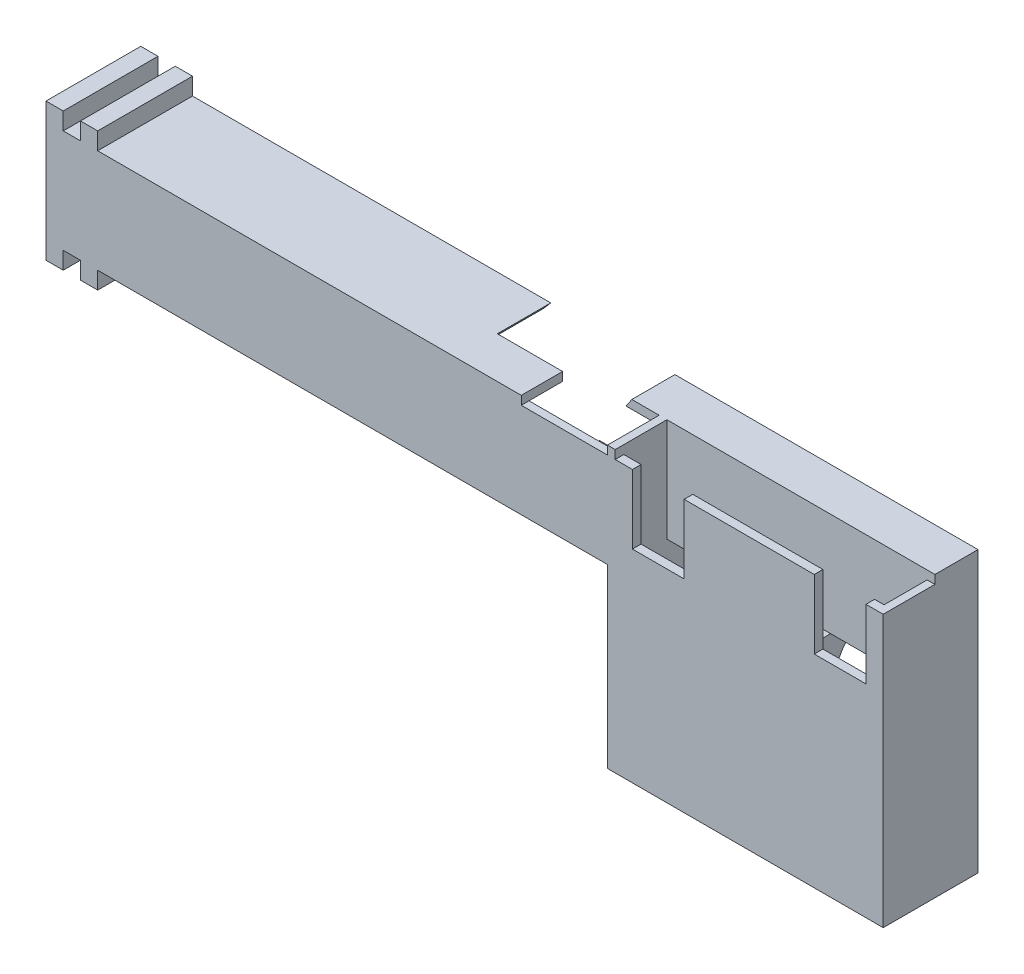
SolidWorks part; units mm, degrees
ref_plane "Front Plane" through (0, 0, 0) normal (0, 0, 1) x (1, 0, 0)
ref_plane "Top Plane" through (0, 0, 0) normal (0, 1, 0) x (1, 0, 0)
ref_plane "Right Plane" through (0, 0, 0) normal (1, 0, 0) x (0, 0, -1)
sketch "Sketch1" plane through (0, 0, 0) normal (0, 0, 1) x (1, 0, 0)
  line L3 (0, 20.5) -> (32, 20.5)
  line L4 (0.9, 20.5) -> (0.9, 31.5)
  line L5 (31.1, 20.5) -> (31.1, 31.5)
  line L6 (0.9, 31.5) -> (31.1, 31.5)
  line L7 (0.9, 20.5) -> (0.9, 6)
  line L8 (31.1, 20.5) -> (31.1, 6)
  line L9 (0.9, 6) -> (31.1, 6)
  line L10 (0, 20.5) -> (0, 0)
  line L11 (0, 0) -> (32, 0)
  line L12 (32, 0) -> (32, 20.5)
  line L13 (0, 20.5) -> (0, 31.5)
  line L14 (0, 31.5) -> (0.9, 31.5)
  line L15 (0, 31.5) -> (0.9, 31.5)
  line L16 (32, 20.5) -> (32, 31.5)
  line L17 (32, 31.5) -> (31.1, 31.5)
  line L21 (0, 31.5) -> (0.9, 31.5)
  line L22 (31.1, 31.5) -> (32, 31.5)
  line L31 (0, 31.5) -> (32, 31.5)
  line L41 (12.1, 20.5) -> (19.9, 20.5)
  line L42 (12.1, 20.5) -> (12.1, 6)
  line L43 (12.1, 6) -> (19.9, 6)
  line L44 (19.9, 20.5) -> (19.9, 6)
  point P0 (0, 0)
  point P11 (0, 20.5)
  point P32 (16, 6)
  point P40 (16, 20.5)
  dimension "D2" = 6
  dimension "D3" = 0.9
  dimension "D6" = 11
  dimension "D7" = 14.5
  dimension "D8" = 0.9
  dimension "D9" = 32
  dimension "D18" = 7.8
  dimension "D19" = 3.9
extrude "Boss-Extrude2" add sketch "Sketch1<3>" along normal blind 11 contours L11 L12 L3 L8 L9 L7 L10 | L14 L13 L3 L4 | L16 L17 L5 L3 | L4 L14 L13 region at (0.45, 26, 0) region at (16, 4.2266, 0) region at (31.55, 26, 0)
sketch "Sketch1<3>" plane through (0, 0, 0) normal (0, 0, 1) x (1, 0, 0) same geometry as "Sketch1"
extrude "Boss-Extrude3" add sketch "Sketch1<4>" along normal blind 5 contours L6 L4 L3 L5 region at (16, 26, 0)
sketch "Sketch1<4>" plane through (0, 0, 0) normal (0, 0, 1) x (1, 0, 0) same geometry as "Sketch1"
sketch "Sketch2" plane through (0, 6, 0) normal (0, 1, 0) x (1, 0, 0)
  line L0 (0.9, -11) -> (0.9, -10)
  line L1 (0.9, -11) -> (0.9, -5) construction
  line L2 (31.1, -11) -> (31.1, -10)
  line L3 (31.1, -11) -> (31.1, 0) construction
  line L4 (0.9, -10) -> (31.1, -10)
  line L5 (0.9, -11) -> (31.1, -11)
  dimension "D1" = 1
extrude "Boss-Extrude4" add sketch "Sketch2" along normal blind 25.5
extrude "Boss-Extrude5" add sketch "Sketch1" along normal blind 11 contours L44 L3 L42 L9 region at (16, 13.25, 0)
sketch "Sketch3" plane through (0, 0, 10) normal (0, 0, -1) x (-1, 0, 0)
  line L0 (-12.1, 6) -> (-12.1, 20.5) construction
  line L1 (-0.9, 6) -> (-12.1, 6)
  line L2 (-0.9, 6) -> (-0.9, 17)
  line L3 (-0.9, 17) -> (-12.1, 17)
  line L4 (-12.1, 6) -> (-12.1, 17)
  line L5 (-19.9, 6) -> (-19.9, 20.5) construction
  line L6 (-31.1, 6) -> (-19.9, 6)
  line L7 (-31.1, 6) -> (-31.1, 17)
  line L8 (-31.1, 17) -> (-19.9, 17)
  line L9 (-19.9, 6) -> (-19.9, 17)
  dimension "D1" = 11
  dimension "D2" = 11
extrude "Boss-Extrude6" add sketch "Sketch3" along normal blind 5
sketch "Sketch4" plane through (0, 31.5, 0) normal (0, 1, 0) x (1, 0, 0)
  line L0 (0, 0) -> (32, 0) construction
  line L1 (0, -0.4) -> (31.1, -0.4)
  line L2 (0, -0.4) -> (0, -4.4)
  line L3 (0, -4.4) -> (31.1, -4.4)
  line L4 (31.1, -0.4) -> (31.1, -4.4)
  line L6 (31.1, -10) -> (31.1, -5) construction
  line L8 (0, -11) -> (0, 0) construction
  dimension "D1" = 0.4
  dimension "D2" = 4
extrude "Cut-Extrude1" cut sketch "Sketch4" against normal blind 10
sketch "Sketch5" plane through (0, 31.5, 0) normal (0, 1, 0) x (1, 0, 0)
  line L0 (0, -11) -> (0, -4.4) construction
  line L1 (32, 0) -> (0, 0)
  line L2 (32, 0) -> (32, -5)
  line L3 (32, -5) -> (0, -5)
  line L4 (0, 0) -> (0, -5)
  line L5 (0.9, -5) -> (31.1, -5) construction
extrude "Boss-Extrude7" add sketch "Sketch5" along normal blind 1
sketch "Sketch7" plane through (0, 0, 0) normal (-1, 0, 0) x (0, 0, 1)
  line L0 (0, 32.5) -> (0, 0) construction
  line L1 (5, 32.5) -> (0, 32.5)
  line L2 (5, 32.5) -> (5, 31.5)
  line L3 (5, 31.5) -> (0, 31.5)
  line L4 (0, 32.5) -> (0, 31.5)
  line L5 (11, 31.5) -> (5, 31.5) construction
  line L6 (4.4, 21.5) -> (4.4, 31.5) construction
  line L7 (0, 21.5) -> (5, 21.5)
  line L8 (0, 21.5) -> (0, 20.4962)
  line L9 (0, 20.4962) -> (5, 20.4962)
  line L10 (5, 21.5) -> (5, 20.4962)
  line L11 (5, 31.5) -> (5, 21.5)
  line L12 (4.4, 31.5) -> (4.4, 21.5)
  line M5 (0.4, 31.5) -> (4.4, 31.5)
  line M7 (4.4, 21.5) -> (0.4, 21.5)
  line M10 (5, 31.5) -> (5, 32.5)
  line M11 (5, 32.5) -> (0, 32.5)
  line M12 (0, 32.5) -> (0, 0)
  dimension "D1" = 1.0038
  dimension "D2" = 5
extrude "Boss-Extrude8" add sketch "Sketch7" along normal blind 62.24 contours L10 L7 L9 M7 M12 | L3 M10 M11 M12 M5 region at (0, 32, 2.5) region at (0, 20.9981, 2.5)
sketch "Sketch8" plane through (0, 0, 5) normal (0, 0, 1) x (1, 0, 0)
  line L0 (-62.24, 32.5) -> (32, 32.5) construction
  line L1 (0.9, 31.5) -> (0, 31.5)
  line L2 (0.9, 31.5) -> (0.9, 32.5)
  line L3 (0.9, 32.5) -> (0, 32.5)
  line L4 (0, 31.5) -> (0, 32.5)
  line L5 (0, 31.5) -> (0, 0) construction
extrude "Boss-Extrude9" add sketch "Sketch8" along normal blind 6
sketch "Sketch9" plane through (0, 0, 0) normal (-1, 0, 0) x (0, 0, 1)
  line L0 (11, 32.5) -> (11, 0) construction
  line L3 (11, 31.5) -> (5, 31.5)
  line L5 (5, 20.4962) -> (11, 20.4962)
  line L6 (5, 20.4962) -> (5, 21.4995)
  line L7 (5, 21.4995) -> (11, 21.4995)
  line L8 (11, 20.4962) -> (11, 21.4995)
  line L10 (11, 31.5) -> (10.1, 31.5)
  line L11 (11, 31.5) -> (11, 21.4995)
  line L12 (11, 21.4995) -> (10.1, 21.4995)
  line L13 (10.1, 31.5) -> (10.1, 21.4995)
  line M1 (11, 0) -> (11, 32.5)
  line M7 (5, 21.5) -> (5, 20.4962)
  dimension "D1" = 1.0033
  dimension "D2" = 0.9
extrude "Boss-Extrude10" add sketch "Sketch9" along normal blind 62.26 contours L7 L5 M7 M1 | L3 L13 L7 M1 region at (0, 26.4998, 10.55) region at (0, 20.9978, 8)
sketch "Sketch10" plane through (0, 0, 5) normal (0, 0, 1) x (1, 0, 0)
  line L0 (-62.24, 32.5) -> (0, 32.5) construction
  line L1 (-10, 32.5) -> (-62.24, 32.5)
  line L2 (-10, 32.5) -> (-10, 31.5)
  line L3 (-10, 31.5) -> (-62.24, 31.5)
  line L4 (-62.24, 32.5) -> (-62.24, 31.5)
  dimension "D1" = 10
extrude "Boss-Extrude11" add sketch "Sketch10" along normal blind 6
sketch "Sketch11" plane through (0, 0, 0) normal (0, 0, -1) x (-1, 0, 0)
  circle A0 centre (71.2419, 77.6773) radius 81.7
  circle A1 centre (71.2419, 77.6773) radius 70.15
  point P0 (71.2419, 77.6773)
  dimension "D3" = 163.4
  dimension "D4" = 140.3
  dimension "D1" = 129.2
  dimension "D2" = 105.4
extrude "Cut-Extrude2" cut sketch "Sketch11" against normal blind 6.2
sketch "Sketch12" plane through (-62.24, 0, 0) normal (-1, 0, 0) x (0, 0, 1)
  line L0 (11, 31.5) -> (11, 21.5)
  line L1 (0, 21.5) -> (11, 21.5)
  line L2 (0, 21.5) -> (0, 20.4962)
  line L3 (0, 20.4962) -> (11, 20.4962)
  line L4 (11, 21.5) -> (11, 20.4962)
  line L5 (0, 32.5) -> (11, 32.5)
  line L6 (0, 32.5) -> (0, 31.5)
  line L7 (0, 31.5) -> (11, 31.5)
  line L8 (11, 32.5) -> (11, 31.5)
  line L9 (10.1, 31.5) -> (11, 31.5)
  line L10 (10.1, 31.5) -> (10.1, 21.5)
  line L11 (10.1, 21.5) -> (11, 21.5)
  line L12 (11, 31.5) -> (11, 21.5)
  line L14 (11, 20.4962) -> (11, 31.5) construction
  line M5 (5, 21.4995) -> (5, 21.5)
  line M6 (5, 21.5) -> (0, 21.5)
  line M7 (0, 21.5) -> (0, 20.4962)
  line M8 (0, 20.4962) -> (5, 20.4962)
  line M9 (5, 20.4962) -> (5, 21.4995)
  dimension "D1" = 11
  dimension "D2" = 1.0038
  dimension "D3" = 1
  dimension "D4" = 0.9
extrude "Boss-Extrude12" add sketch "Sketch12" along normal blind 2.91 contours L8 L5 L6 L7 | L7 L10 L1 L0 | L4 L1 L3 M5 M9 | M9 M5 M6 M7 M8 region at (-62.24, 26.5, 10.55) region at (-62.24, 32, 5.5) region at (-62.24, 20.9981, 8) region at (-62.24, 20.9981, 2.5)
sketch "Sketch14" plane through (0, 20.4962, 0) normal (0, -1, 0) x (-1, 0, 0)
  line L0 (65.15, 0) -> (30.6051, 0) construction
  line L1 (65.15, -11) -> (63.15, -11)
  line L2 (65.15, -11) -> (65.15, 0)
  line L3 (65.15, 0) -> (63.15, 0)
  line L4 (63.15, -11) -> (63.15, 0)
  line L5 (65.15, -11) -> (0, -11) construction
  line L6 (59.15, 0) -> (61.15, 0)
  line L7 (59.15, 0) -> (59.15, -11)
  line L8 (59.15, -11) -> (61.15, -11)
  line L9 (61.15, 0) -> (61.15, -11)
  dimension "D1" = 2
  dimension "D2" = 2
  dimension "D3" = 2
extrude "Boss-Extrude13" add sketch "Sketch14" along normal blind 2
sketch "Sketch15" plane through (0, 32.5, 0) normal (0, 1, 0) x (1, 0, 0)
  line L0 (-10, -11) -> (-65.15, -11) construction
  line L1 (-65.15, 0) -> (-63.15, 0)
  line L2 (-65.15, 0) -> (-65.15, -11)
  line L3 (-65.15, -11) -> (-63.15, -11)
  line L4 (-63.15, 0) -> (-63.15, -11)
  line L5 (-61.15, 0) -> (-59.15, 0)
  line L6 (-61.15, 0) -> (-61.15, -11)
  line L7 (-61.15, -11) -> (-59.15, -11)
  line L8 (-59.15, 0) -> (-59.15, -11)
  dimension "D1" = 2
extrude "Boss-Extrude14" add sketch "Sketch15" along normal blind 2
sketch "Sketch20" plane through (19.9, 0, 0) normal (1, 0, 0) x (0, 0, -1)
  line L0 (0, 20.5) -> (0, 6) construction
  line L1 (-5, 6) -> (-5, 17) construction
  ellipse E0 centre (0, 13.25) end of major axis (0, 6) minor radius 5
  dimension "D1" = 7.25
  dimension "D2" = 10
extrude "Cut-Extrude3" cut sketch "Sketch20" against normal blind 10
sketch "Sketch21" plane through (0, 0, 11) normal (0, 0, 1) x (1, 0, 0)
  line L0 (32, 31.5) -> (0.9, 31.5) construction
  line L1 (2.9, 31.5) -> (8.9, 31.5)
  line L2 (2.9, 31.5) -> (2.9, 23.5)
  line L3 (2.9, 23.5) -> (8.9, 23.5)
  line L4 (8.9, 31.5) -> (8.9, 23.5)
  line L6 (24, 31.5) -> (30, 31.5)
  line L7 (24, 31.5) -> (24, 23.5)
  line L8 (24, 23.5) -> (30, 23.5)
  line L9 (30, 31.5) -> (30, 23.5)
  dimension "D1" = 2
  dimension "D2" = 2
  dimension "D3" = 6
  dimension "D4" = 6
  dimension "D5" = 8
  dimension "D6" = 8
extrude "Cut-Extrude4" cut sketch "Sketch21" against normal blind 1
